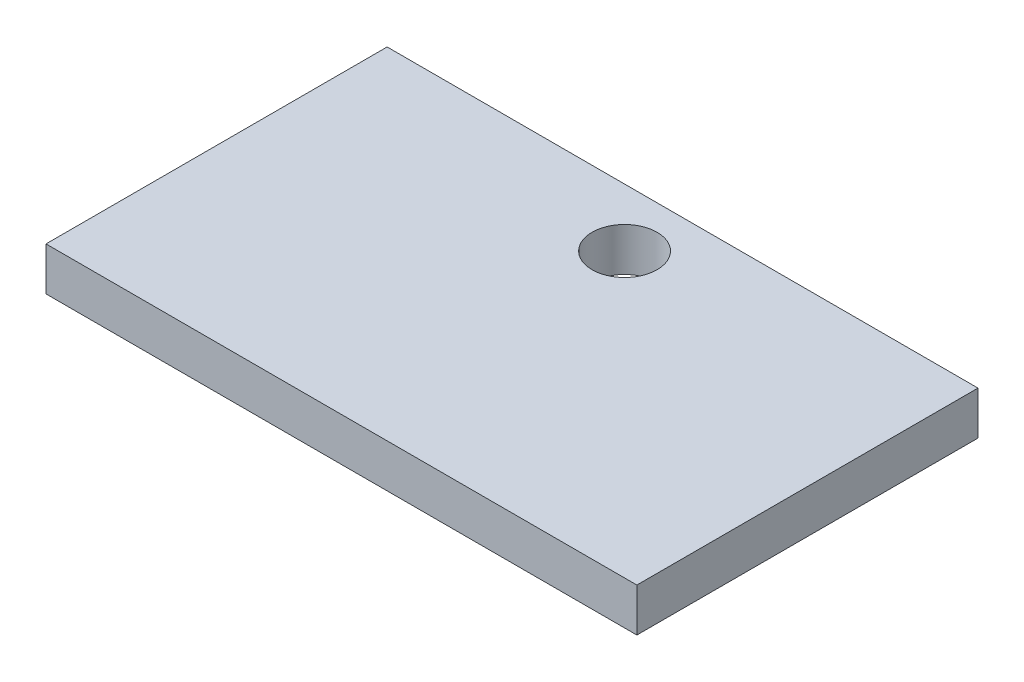
SolidWorks part; units mm, degrees
material "ABS"
ref_plane "Plan de face" through (0, 0, 0) normal (0, 0, 1) x (1, 0, 0)
ref_plane "Plan de dessus" through (0, 0, 0) normal (0, 1, 0) x (1, 0, 0)
ref_plane "Plan de droite" through (0, 0, 0) normal (1, 0, 0) x (0, 0, -1)
sketch "Esquisse2" plane through (0, 0, 0) normal (0, 1, 0) x (1, 0, 0)
  line L0 (-43.3013, 0) -> (43.3013, 0) construction
  line L1 (-43.3013, 25) -> (43.3013, 25)
  line L2 (-43.3013, 25) -> (-43.3013, -25)
  line L3 (-43.3013, -25) -> (43.3013, -25)
  line L4 (43.3013, 25) -> (43.3013, -25)
  line L5 (0, 100) -> (-43.3013, 25) construction
  line L6 (0, 100) -> (43.3013, 25) construction
  line L7 (0, 100) -> (0, 0) construction
  circle A0 centre (0, 100) radius 75 construction
  point P8 (0, 0)
  dimension "D2" = 150
  dimension "D1" = 50
  dimension "D3" = 60
extrude "Boss.-Extru.1" add sketch "Esquisse2" along normal blind 6.35
sketch "Sketch1" plane through (0, 6.35, 0) normal (0, 1, 0) x (1, 0, 0)
  circle A0 centre (0, 16.5) radius 4.7625
  circle A1 centre (0, 16.5) radius 7.1438 construction
  dimension "D1" = 9.525
  dimension "D2" = 0
extrude "Cut-Extrude1" cut sketch "Sketch1" against normal up to surface (6.35 mm away) up to face at (0, 0, 0)
